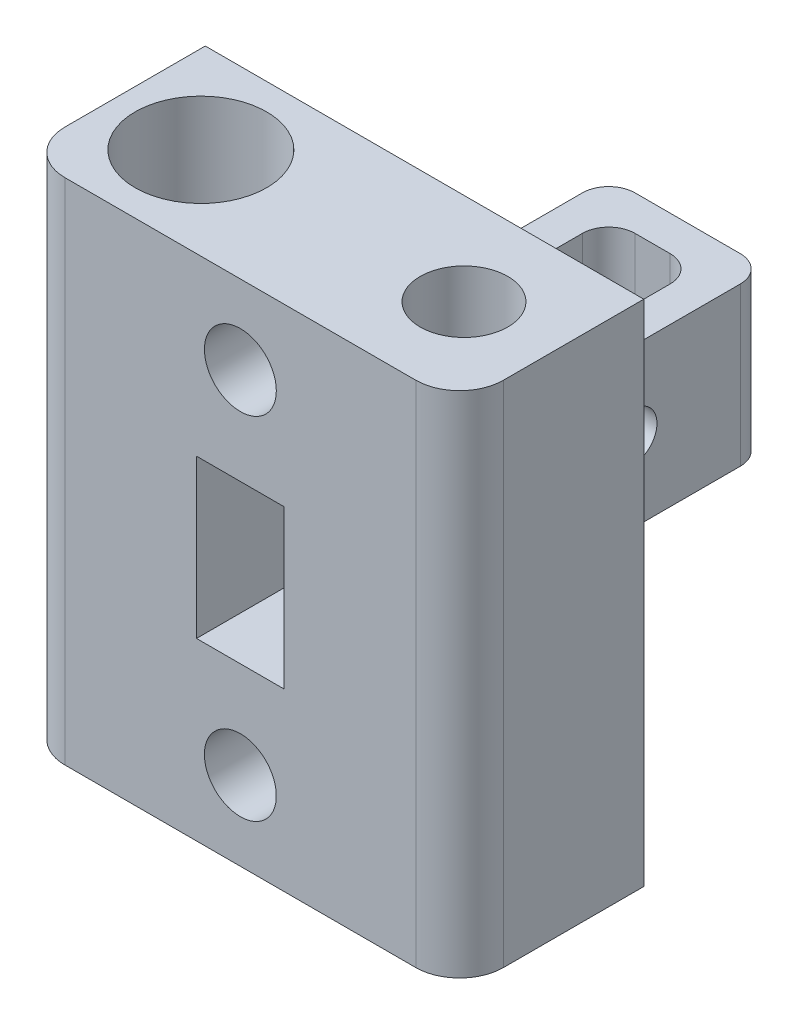
SolidWorks part; units mm, degrees
ref_plane "Front Plane" through (0, 0, 0) normal (0, 0, 1) x (1, 0, 0)
ref_plane "Top Plane" through (0, 0, 0) normal (0, 1, 0) x (1, 0, 0)
ref_plane "Right Plane" through (0, 0, 0) normal (1, 0, 0) x (0, 0, -1)
sketch "Sketch1" plane through (0, 0, 0) normal (0, 1, 0) x (1, 0, 0)
  line L1 (-25, 10.5) -> (25, 10.5)
  line L2 (-25, 10.5) -> (-25, -10.5)
  line L3 (-25, -10.5) -> (25, -10.5)
  line L4 (25, 10.5) -> (25, -10.5)
  line L5 (-25, 10.5) -> (25, -10.5) construction
  line L6 (-25, -10.5) -> (25, 10.5) construction
  point P0 (0, 0)
  dimension "D1" = 21
  dimension "D2" = 50
extrude "Boss-Extrude1" add sketch "Sketch1" along normal blind 58
sketch "Sketch3" plane through (0, 58, 0) normal (0, 1, 0) x (1, 0, 0)
  line L0 (-15, 0) -> (15, 0) construction
  circle A0 centre (-15, 0) radius 7.5
  dimension "D1" = 15
  dimension "D2" = 30
extrude "Cut-Extrude1" cut sketch "Sketch3" against normal blind 24 contours A0
sketch "Sketch4" plane through (0, 58, 0) normal (0, 1, 0) x (1, 0, 0)
  line L0 (-15, 0) -> (15, 0) construction
  circle A0 centre (15, 0) radius 5
  dimension "D1" = 10
extrude "Cut-Extrude2" cut sketch "Sketch4" against normal up to next
sketch "Sketch5" plane through (0, 0, 0) normal (0, -1, 0) x (1, 0, 0)
  circle A1 centre (-15, 0) radius 7.5
  circle A2 centre (-15, 0) radius 7.5
  dimension "D1" = 0
extrude "Cut-Extrude3" cut sketch "Sketch5" against normal blind 24
sketch "Sketch6" plane through (0, 0, 0) normal (0, -1, 0) x (1, 0, 0)
  circle A0 centre (-15, 0) radius 4.5
extrude "Cut-Extrude4" cut sketch "Sketch6" against normal up to next
sketch "Sketch7" plane through (0, 0, 10.5) normal (0, 0, 1) x (1, 0, 0)
  line L0 (0, 58) -> (0, 0) construction
  line L1 (-25, 58) -> (25, 58) construction
  line L2 (-25, 0) -> (25, 0) construction
  line L3 (-25, 29) -> (25, 29) construction
  line L4 (-25, 58) -> (-25, 0) construction
  line L5 (25, 58) -> (25, 0) construction
  circle A1 centre (0, 49) radius 4.1
  circle A2 centre (0, 9) radius 4.1
  point P24 (0, 9)
  dimension "D1" = 8.2
  dimension "D2" = 9
sketch "Sketch8" plane through (0, 0, 10.5) normal (0, 0, 1) x (1, 0, 0)
  line L0 (-25, 29) -> (25, 29) construction
  line L1 (-25, 58) -> (-25, 0) construction
  line L2 (25, 58) -> (25, 0) construction
  line L3 (0, 58) -> (0, 0) construction
  line L4 (-25, 58) -> (25, 58) construction
  line L6 (-5, 20) -> (5, 20)
  line L7 (-5, 20) -> (-5, 38)
  line L8 (-5, 38) -> (5, 38)
  line L9 (5, 20) -> (5, 38)
  line L10 (-5, 20) -> (5, 38) construction
  line L11 (-5, 38) -> (5, 20) construction
  point P11 (0, 29)
  dimension "D1" = 18
  dimension "D2" = 10
extrude "Cut-Extrude5" cut sketch "Sketch8" against normal up to next
sketch "Sketch10" plane through (0, 0, -10.5) normal (0, 0, -1) x (-1, 0, 0)
  line L0 (-25, 29) -> (25, 29) construction
  line L1 (-25, 58) -> (-25, 0) construction
  line L2 (25, 58) -> (25, 0) construction
  line L3 (0, 58) -> (0, 0) construction
  line L4 (-25, 58) -> (25, 58) construction
extrude "Cut-Extrude6" cut sketch "Sketch7" against normal blind 15
sketch "Sketch11" plane through (0, 0, -10.5) normal (0, 0, -1) x (-1, 0, 0)
  line L0 (-25, 29) -> (25, 29) construction
  line L1 (9, 38) -> (5, 38)
  line L2 (9, 38) -> (9, 20)
  line L3 (9, 20) -> (5, 20)
  line L4 (5, 38) -> (5, 20)
  line L5 (9, 38) -> (5, 20) construction
  line L6 (9, 20) -> (5, 38) construction
  line L7 (0, 58) -> (0, 0) construction
  line L8 (0, 58) -> (0, 0)
  line L9 (-9, 20) -> (-5, 20)
  line L10 (-5, 38) -> (-5, 20)
  line L11 (-9, 38) -> (-5, 38)
  line L12 (-9, 38) -> (-9, 20)
  point P0 (7, 29)
  line M7 (-5, 20) -> (-5, 38)
  line M9 (5, 38) -> (5, 20)
  dimension "D1" = 5
  dimension "D2" = 4
  dimension "D3" = 18
extrude "Boss-Extrude2" add sketch "Sketch11" along normal blind 26 contours L1 L4 L3 L2 M9 | L11 L12 L9 L10 M7 region at (-7, 29, -10.5) region at (7, 29, -10.5)
sketch "Sketch12" plane through (0, 0, -36.5) normal (0, 0, -1) x (-1, 0, 0)
  line L1 (9, 20) -> (-9, 20)
  line L2 (9, 20) -> (9, 38)
  line L3 (9, 38) -> (-9, 38)
  line L4 (-9, 20) -> (-9, 38)
extrude "Boss-Extrude3" add sketch "Sketch12" along normal blind 4
sketch "Sketch13" plane through (9, 0, 0) normal (1, 0, 0) x (0, 0, -1)
  line L3 (10.5, 29) -> (40.5, 29) construction
  line L4 (10.5, 38) -> (10.5, 20) construction
  line L5 (40.5, 38) -> (40.5, 20) construction
  line L6 (16.25, 29) -> (25.25, 29) construction
  line L7 (16.25, 31.75) -> (25.25, 31.75)
  line L8 (16.25, 26.25) -> (25.25, 26.25)
  arc A0 (16.25, 31.75) -> (16.25, 26.25) centre (16.25, 29) ccw
  arc A1 (25.25, 26.25) -> (25.25, 31.75) centre (25.25, 29) ccw
  point P1 (13.5, 29)
  point P14 (20.75, 29)
  dimension "D1" = 5.5
  dimension "D2" = 3
  dimension "D3" = 9
extrude "Cut-Extrude7" cut sketch "Sketch13" against normal through all
fillet "Fillet1" radius 5 2 edges at (-25, 29, 10.5) (25, 29, 10.5)
fillet "Fillet2" radius 5 4 edges at (-7, 20, -10.5) (7, 20, -10.5) (-7, 38, -10.5) (7, 38, -10.5)
fillet "Fillet3" radius 3 4 edges at (-5, 29, -36.5) (5, 29, -36.5) (-9, 29, -40.5) (9, 29, -40.5)
sketch "Sketch14" plane through (0, 0, 0) normal (0, -1, 0) x (1, 0, 0)
  line L0 (20.5508, 5.5508) -> (9.4492, -5.5508) construction
  line L1 (25, -10.5) -> (-25, -10.5) construction
  circle A0 centre (20.5508, 5.5508) radius 1.95
  circle A1 centre (15, 0) radius 5 construction
  circle A2 centre (9.4492, -5.5508) radius 1.95
  circle A3 centre (15, 0) radius 5 construction
  point P7 (0, 0)
  dimension "D1" = 7.85
  dimension "D2" = 3.9
  dimension "D3" = 3.9
  dimension "D4" = 7.85
  dimension "D5" = 45
extrude "Cut-Extrude8" cut sketch "Sketch14" against normal blind 10
